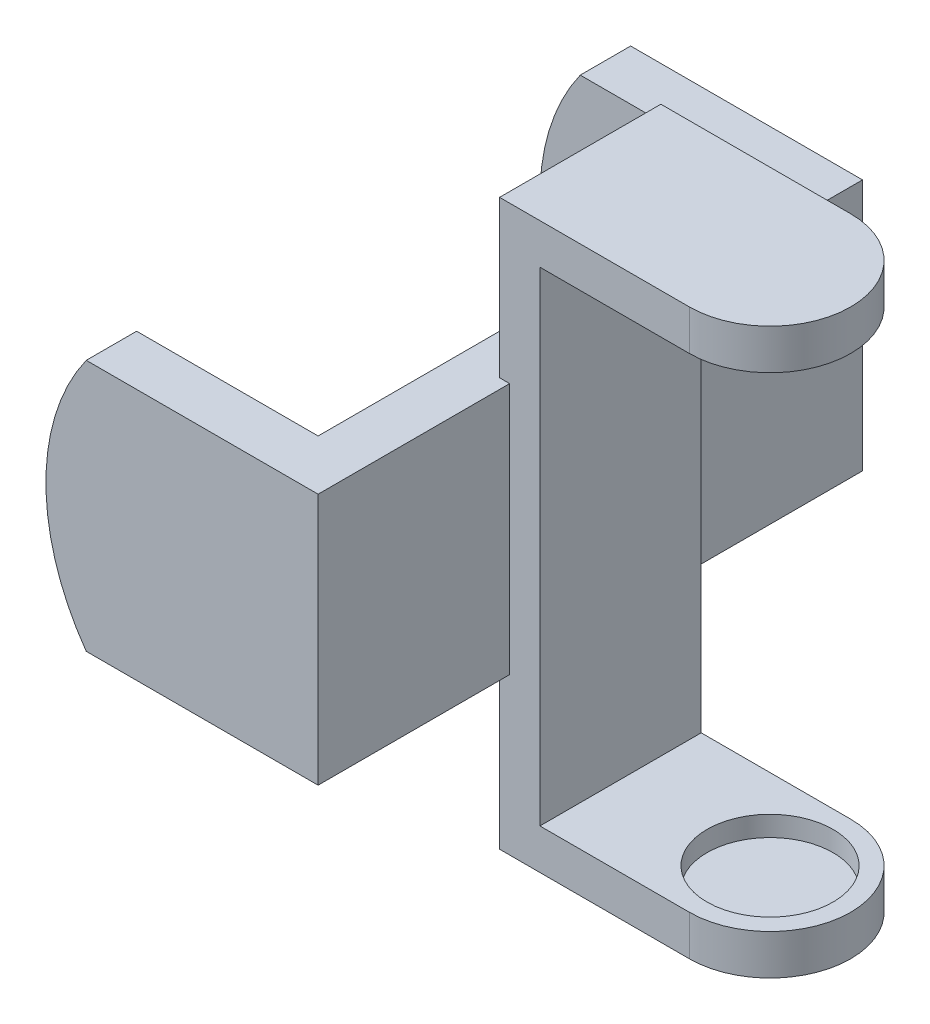
SolidWorks part; units mm, degrees
note: The reader was unsure of these and kept them because the rebuilt part matched: shared geometry of "Sketch2<2>", "Sketch4<4>".
ref_plane "Front Plane" through (0, 0, 0) normal (0, 0, 1) x (1, 0, 0)
ref_plane "Top Plane" through (0, 0, 0) normal (0, 1, 0) x (1, 0, 0)
ref_plane "Right Plane" through (0, 0, 0) normal (1, 0, 0) x (0, 0, -1)
sketch "Sketch1" plane through (0, 0, 0) normal (0, 1, 0) x (1, 0, 0)
  line L0 (0, 0) -> (0, 16)
  line L1 (0, 16) -> (18.8287, 16)
  line L2 (18.8287, 0) -> (0, 0)
  arc A0 (18.8287, 16) -> (18.8287, 0) centre (18.8287, 8) cw
  circle A1 centre (18.8287, 8) radius 1.25 construction
  circle A3 centre (18.8287, 8) radius 8 construction
  dimension "D1" = 2.5
  dimension "D2" = 8
extrude "Boss-Extrude1" add sketch "Sketch1" along normal blind 56 contours A0 L1 L0 L2 A1
shell "Shell1" thickness 4 removed face at (9.4144, 28, -16) removed face at (9.4144, 28, 0) removed face at (22.8287, 28, -8)
sketch "Sketch2" plane through (0, 0, 0) normal (0, -1, 0) x (1, 0, 0)
  circle A0 centre (18.8287, -8) radius 6.25
  dimension "D1" = 12.5
extrude "Cut-Extrude1" cut sketch "Sketch2" along normal blind 2 from surface at -4 starting at face at (13.4144, 4, -8)
extrude "Cut-Extrude2" cut sketch "Sketch2<2>" against normal blind 2 from surface at -52 starting at face at (13.4144, 52, -8)
sketch "Sketch2<2>" plane through (0, 0, 0) normal (0, -1, 0) x (1, 0, 0) same geometry as "Sketch2"
sketch "Sketch3" plane through (0, 0, 0) normal (-1, 0, 0) x (0, 0, 1)
  line L0 (-8, 56) -> (-8, 0) construction
  line L1 (-35, 40.5) -> (19, 40.5)
  line L2 (-35, 40.5) -> (-35, 15.5)
  line L3 (-35, 15.5) -> (19, 15.5)
  line L4 (19, 40.5) -> (19, 15.5)
  line L5 (-35, 40.5) -> (19, 15.5) construction
  line L6 (-35, 15.5) -> (19, 40.5) construction
  line L7 (0, 56) -> (-16, 56) construction
  line L8 (0, 0) -> (-16, 0) construction
  line L9 (0, 56) -> (0, 0) construction
  point P0 (-8, 28)
  point P14 (0, 28)
  dimension "D1" = 54
  dimension "D2" = 25
extrude "Boss-Extrude2" add sketch "Sketch3" against normal blind 1 and the other way blind 4
sketch "Sketch4" plane through (0, 0, 19) normal (0, 0, 1) x (1, 0, 0)
  line L0 (-4, 40.5) -> (-22, 40.5)
  line L1 (-22, 15.5) -> (-4, 15.5)
  line L2 (-4, 15.5) -> (-4, 40.5) construction
  line L3 (-4, 15.5) -> (1, 15.5) construction
  line L4 (-4, 40.5) -> (-4, 15.5)
  arc A1 (-22, 40.5) -> (-22, 15.5) centre (-4.4688, 28) ccw
  point P5 (-26, 28)
  point P9 (-4, 28)
  dimension "D1" = 22
extrude "Boss-Extrude3" add sketch "Sketch4" against normal blind 5
ref_plane "Plane1" through (0, 0, -8) normal (0, 0, -1) x (-1, 0, 0)
extrude "Boss-Extrude4" add sketch "Sketch4<4>" along normal blind 5 from surface at -54 starting at face at (-1.5, 28, -35)
sketch "Sketch4<4>" plane through (0, 0, 19) normal (0, 0, 1) x (1, 0, 0) same geometry as "Sketch4"
